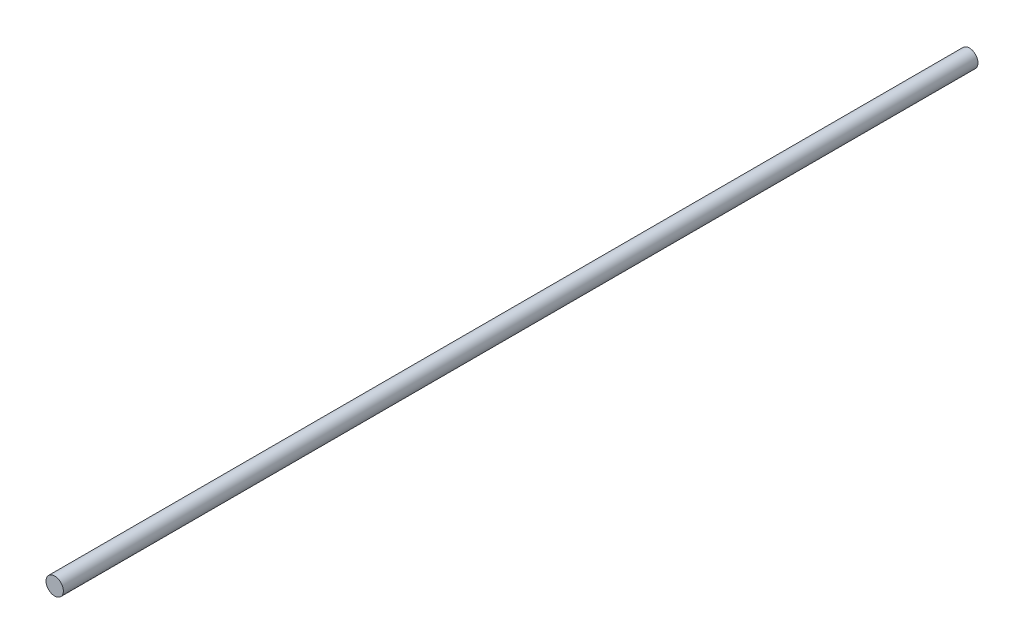
SolidWorks part; units mm, degrees
material "AISI 316 Stainless Steel Sheet (SS)"
ref_plane "Front (1)" through (0, 0, 0) normal (0, 0, 1) x (1, 0, 0)
ref_plane "Top (2)" through (0, 0, 0) normal (0, 1, 0) x (1, 0, 0)
ref_plane "Right (3)" through (0, 0, 0) normal (1, 0, 0) x (0, 0, -1)
ref_axis "X Axis" through (13.5064, 0, 0) along (-1, 0, 0)
ref_axis "Y Axis" through (0, 12.3593, 0) along (0, -1, 0)
ref_axis "Z Axis" through (0, 0, 14.1119) along (0, 0, -1)
sketch "Sketch2" plane through (0, 0, 0) normal (1, 0, 0) x (0, 0, -1)
  line L0 (-89.9, 0) -> (0, 0) construction
  line L1 (-89.9, 0) -> (331.5, 0)
  line L2 (-89.9, 0) -> (-89.9, 4)
  line L3 (-89.9, 4) -> (331.5, 4)
  line L4 (331.5, 0) -> (331.5, 4)
  dimension "D1" = 421.4
  dimension "D2" = 4
revolve "Revolve1" add sketch "Sketch2" angle 360 about L0
cosmetic thread "Cosmetic Thread2" parameters "D2"=6.891
